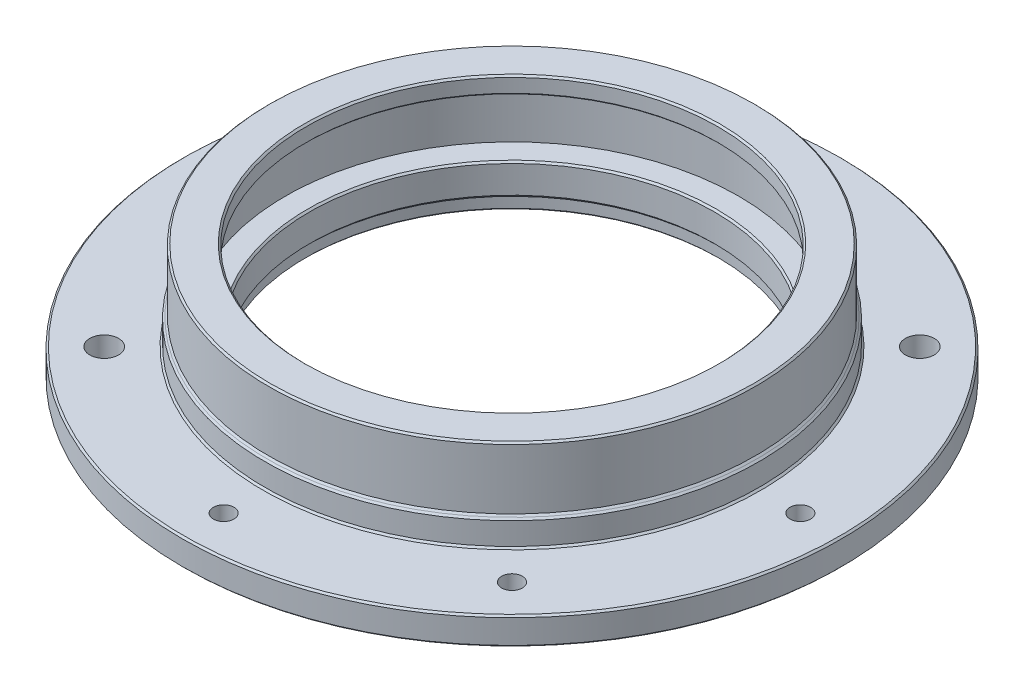
SolidWorks part; units mm, degrees
ref_plane "前视基准面" through (0, 0, 0) normal (0, 0, 1) x (1, 0, 0)
ref_plane "上视基准面" through (0, 0, 0) normal (0, 1, 0) x (1, 0, 0)
ref_plane "右视基准面" through (0, 0, 0) normal (1, 0, 0) x (0, 0, -1)
sketch "草图1" plane through (0, 0, 0) normal (0, 0, 1) x (1, 0, 0)
  line L0 (0, 0) -> (0, 21.7128) construction
  line L1 (-48, 0) -> (-33.25, 0)
  line L2 (-33.25, 0) -> (-33.25, 6.5)
  line L3 (-33.25, 6.5) -> (-33, 6.5)
  line L4 (-33, 6.5) -> (-33, 14.5)
  line L5 (-33, 14.5) -> (-30, 14.5)
  line L6 (-30, 14.5) -> (-30, 17)
  line L7 (-30, 17) -> (-35.5, 17)
  line L8 (-36, 7.75) -> (-36, 4)
  line L9 (-36, 4) -> (-48, 4)
  line L10 (-48, 4) -> (-48, 0)
  line L11 (-36, 7.75) -> (-35.5, 7.75)
  line L12 (-35.5, 7.75) -> (-35.5, 17)
  dimension "D1" = 72
  dimension "D2" = 96
  dimension "D3" = 4
  dimension "D4" = 2.5
  dimension "D5" = 66
  dimension "D6" = 8
  dimension "D7" = 66.5
  dimension "D8" = 13
  dimension "D9" = 60
  dimension "D10" = 2.5
  dimension "D11" = 1.25
revolve "旋转1" add sketch "草图1" angle 360 about L0
sketch "草图2" plane through (0, 4, 0) normal (0, 1, 0) x (1, 0, 0)
  line L0 (-29.6985, 29.6985) -> (29.6985, -29.6985) construction
  line L1 (0, -42) -> (0, 0) construction
  line L2 (0, 0) -> (-29.6985, -29.6985) construction
  circle A0 centre (0, 0) radius 42 construction
  circle A1 centre (-42, 0) radius 1.5
  circle A2 centre (-29.6985, 29.6985) radius 1.5
  circle A3 centre (0, 42) radius 1.5
  circle A5 centre (42, 0) radius 1.5
  circle A6 centre (29.6985, -29.6985) radius 1.5
  circle A7 centre (0, -42) radius 1.5
  circle A9 centre (-29.6985, -29.6985) radius 1.5 [skipped]
  circle A10 centre (29.6985, 29.6985) radius 1.5 [skipped]
  circle A11 centre (-29.6985, -29.6985) radius 2.1
  circle A13 centre (29.6985, 29.6985) radius 2.1
  point P21 (0, 0)
  dimension "D1" = 84
  dimension "D2" = 3
  dimension "D4" = 4.2
  dimension "D5" = 45
  dimension "D3" = 8
extrude "切除-拉伸1" cut sketch "草图2" against normal through all
cosmetic thread "装饰螺纹线1" parameters "D2"=4
cosmetic thread "装饰螺纹线2" parameters "D2"=4
cosmetic thread "装饰螺纹线3" parameters "D2"=4
cosmetic thread "装饰螺纹线4" parameters "D2"=4
cosmetic thread "装饰螺纹线5" parameters "D2"=4
cosmetic thread "装饰螺纹线6" parameters "D2"=4
chamfer "倒角1" distance 0.25 angle 45 9 edges at (0, 14.5, -30) (0, 17, -30) (0, 4, -36) (0, 4, -48) (0, 0, -48) (0, 0, -33.25) (0, 7.75, -36) (0, 17, -35.5) (0, 7.75, -35.5)
sketch "草图3" plane through (0, 0, 0) normal (0, 0, 1) x (1, 0, 0)
  line L0 (-33.25, 0) -> (-33.25, 6.5)
  line L1 (-33.25, 6.5) -> (-29.5, 6.5)
  line L4 (-29.5, 6.5) -> (-29.5, 2)
  line L5 (-47.75, 0) -> (47.75, 0) construction
  line L6 (-30, 0) -> (-33.25, 0)
  line L7 (0, 0) -> (0, 21.7128) construction
  line L8 (0, 0) -> (0, 21.7128) construction
  line L9 (-30, 2) -> (-29.5, 2)
  line L12 (-30, 2) -> (-30, 0)
  dimension "D1" = 59
  dimension "D2" = 2
  dimension "D5" = 60
revolve "旋转2" add sketch "草图3" angle 360 about L8
chamfer "倒角2" distance 0.25 angle 45 6 edges at (0, 6.5, -29.5) (0, 6.5, -33.25) (0, 0, -33.25) (0, 0, -30) (0, 2, -30) (0, 2, -29.5)
move or copy body "实体-移动/复制1" [suppressed] bodies to move or copy 107 108
